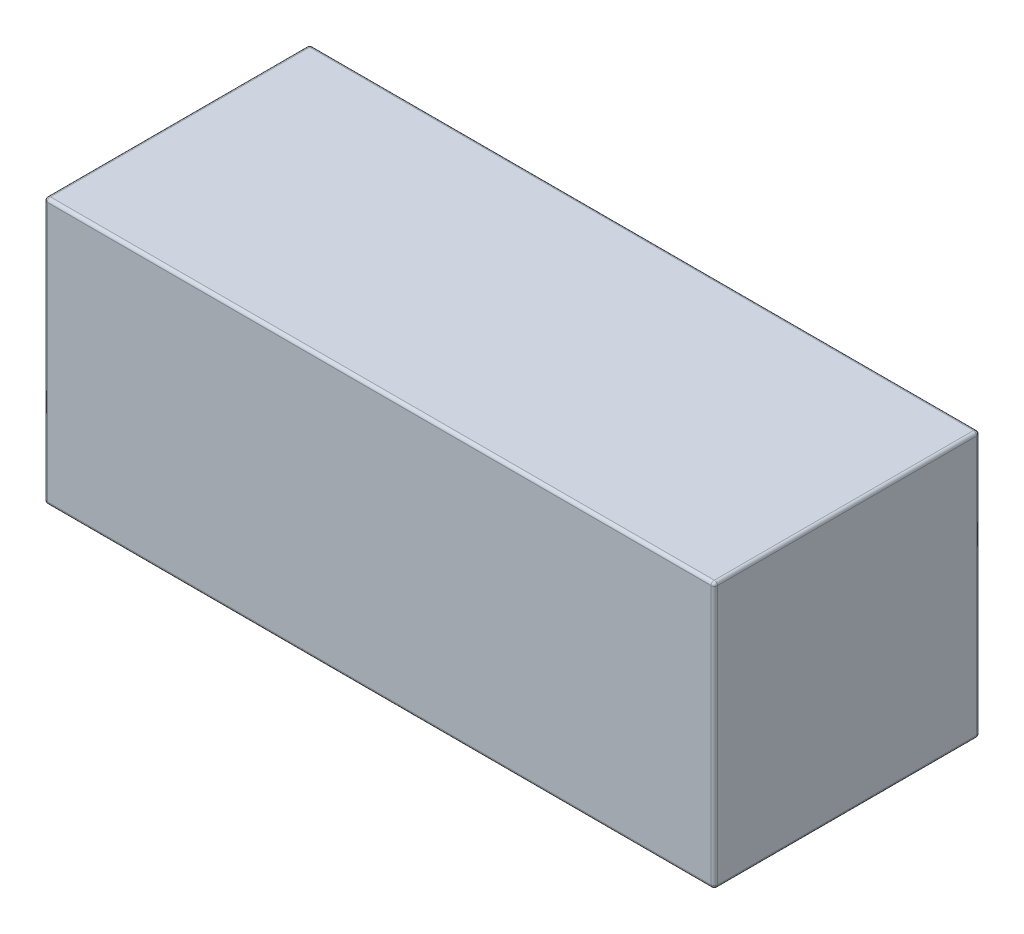
SolidWorks part; units mm, degrees
ref_plane "Plan de face" through (0, 0, 0) normal (0, 0, 1) x (1, 0, 0)
ref_plane "Plan de dessus" through (0, 0, 0) normal (0, 1, 0) x (1, 0, 0)
ref_plane "Plan de droite" through (0, 0, 0) normal (1, 0, 0) x (0, 0, -1)
sketch "Esquisse1" plane through (0, 0, 0) normal (0, 0, 1) x (1, 0, 0)
  line L1 (0, 0) -> (106, 0)
  line L2 (0, 0) -> (0, -42)
  line L3 (0, -42) -> (106, -42)
  line L4 (106, 0) -> (106, -42)
  dimension "D1" = 106
  dimension "D2" = 42
extrude "Boss.-Extru.1" add sketch "Esquisse1" along normal blind 42
sketch "Esquisse2" plane through (0, -42, 0) normal (0, -1, 0) x (1, 0, 0)
  line L1 (59.75, 38.25) -> (70.25, 38.25)
  line L2 (59.75, 38.25) -> (59.75, 27.75)
  line L3 (59.75, 27.75) -> (70.25, 27.75)
  line L4 (70.25, 38.25) -> (70.25, 27.75)
  line L6 (0, 0) -> (106, 0) construction
  line L7 (106, 42) -> (106, 0) construction
  line L10 (0, 42) -> (106, 42) construction
  line L13 (59.75, 14.25) -> (70.25, 14.25)
  line L14 (59.75, 14.25) -> (59.75, 3.75)
  line L15 (59.75, 3.75) -> (70.25, 3.75)
  line L16 (70.25, 14.25) -> (70.25, 3.75)
  point P4 (70.25, 9)
  point P7 (106, 21)
  point P10 (53, 42)
  point P11 (65, 38.25)
  point P16 (65, 3.75)
  point P18 (70.1818, 15.75)
  point P20 (53, 0)
  point P21 (70.25, 33)
  dimension "D1" = 10.5
  dimension "D2" = 10.5
  dimension "D3" = 10.5
  dimension "D4" = 10.5
  dimension "D5" = 12
  dimension "D6" = 12
  dimension "D7" = 12
  dimension "D8" = 12
extrude "Enlèv. mat.-Extru.1" cut sketch "Esquisse2" against normal blind 4.5
ref_plane "Plan1" through (0, 0, 21) normal (0, 0, 1) x (1, 0, 0)
ref_plane "Plan2" through (53, 0, 0) normal (1, 0, 0) x (0, 0, -1)
ref_plane "Plan3" through (37, 0, 37) normal (0.7071, 0, 0.7071) x (0.7071, 0, -0.7071)
fillet "Congé1" radius 0.5 12 edges at (0, -42, 21) (53, -42, 42) (0, -21, 42) (106, -42, 21) (106, -21, 42) (53, -42, 0) (106, -21, 0) (0, -21, 0) (106, 0, 21) (53, 0, 42) (0, 0, 21) (53, 0, 0)
mirror "Symétrie1" about plane through (53, 0, 0) normal (1, 0, 0) of "Enlèv. mat.-Extru.1"
